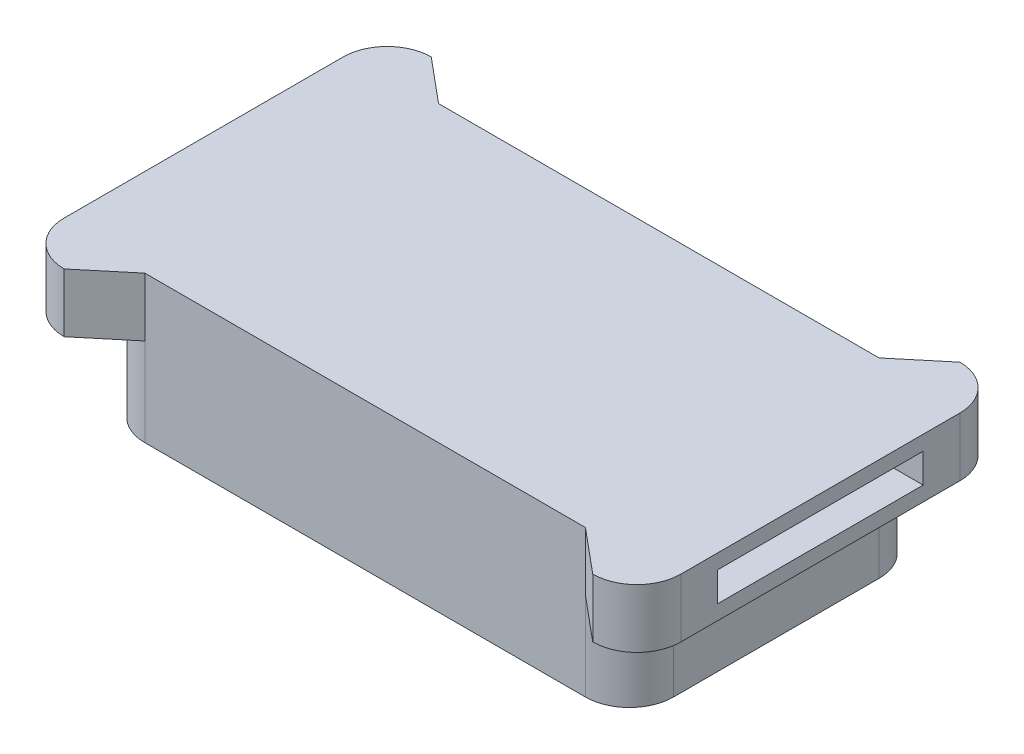
SolidWorks part; units mm, degrees
ref_plane "Front Plane" through (0, 0, 0) normal (0, 0, 1) x (1, 0, 0)
ref_plane "Top Plane" through (0, 0, 0) normal (0, 1, 0) x (1, 0, 0)
ref_plane "Right Plane" through (0, 0, 0) normal (1, 0, 0) x (0, 0, -1)
sketch "Sketch2" plane through (0, 0, 0) normal (0, 1, 0) x (1, 0, 0)
  line L4 (-9, 6.25) -> (-7.5, 5)
  line L5 (-7.5, 5) -> (7.5, 5)
  line L6 (-9, 3.5) -> (-9, -3.5)
  line L11 (-7.5, -5) -> (7.5, -5)
  line L12 (9, 3.5) -> (9, -3.5)
  line L13 (-9, 5) -> (9, -5) construction
  line L14 (-9, -5) -> (9, 5) construction
  line L16 (-10.5, 4.75) -> (-10.5, -4.75)
  line L18 (10.5, 4.75) -> (10.5, -4.75)
  line L19 (-10.5, 6.25) -> (10.5, -6.25) construction
  line L20 (-10.5, -6.25) -> (10.5, 6.25) construction
  line L21 (6.75, 4.25) -> (-6.75, 4.25)
  line L22 (8.25, 2.75) -> (8.25, -2.75)
  line L23 (6.75, -4.25) -> (-6.75, -4.25)
  line L24 (-8.25, 2.75) -> (-8.25, -2.75)
  line L25 (8.25, 4.25) -> (-8.25, -4.25) construction
  line L26 (8.25, -4.25) -> (-8.25, 4.25) construction
  line L27 (7.5, 5) -> (9, 6.25)
  line L28 (-7.5, -5) -> (-9, -6.25)
  line L29 (7.5, -5) -> (9, -6.25)
  arc A8 (-7.5, -5) -> (-9, -3.5) centre (-7.5, -3.5) cw
  arc A9 (7.5, -5) -> (9, -3.5) centre (7.5, -3.5) ccw
  arc A10 (9, 3.5) -> (7.5, 5) centre (7.5, 3.5) ccw
  arc A11 (-7.5, 5) -> (-9, 3.5) centre (-7.5, 3.5) ccw
  arc A12 (9, 6.25) -> (10.5, 4.75) centre (9, 4.75) cw
  arc A13 (9, -6.25) -> (10.5, -4.75) centre (9, -4.75) ccw
  arc A14 (-9, -6.25) -> (-10.5, -4.75) centre (-9, -4.75) cw
  arc A15 (-10.5, 4.75) -> (-9, 6.25) centre (-9, 4.75) cw
  arc A16 (6.75, 4.25) -> (8.25, 2.75) centre (6.75, 2.75) cw
  arc A17 (8.25, -2.75) -> (6.75, -4.25) centre (6.75, -2.75) cw
  arc A18 (-6.75, -4.25) -> (-8.25, -2.75) centre (-6.75, -2.75) cw
  arc A19 (-8.25, 2.75) -> (-6.75, 4.25) centre (-6.75, 2.75) cw
  point P5 (0, 0)
  point P6 (0, 0)
  point P35 (0, 0)
  dimension "D1" = 1.5
  dimension "D6" = 10
  dimension "D9" = 1.5
  dimension "D2" = 21
  dimension "D3" = 0
  dimension "D4" = 0
  dimension "D5" = 18
  dimension "D7" = 8.5
  dimension "D8" = 16.5
extrude "Boss-Extrude1" add sketch "Sketch2" along normal blind 2 and the other way blind 3 contours L5 A11 L6 A8 L11 A9 L12 A10 L24 A19 L21 A16 L22 A17 L23 A18 region at (0, 0, -4.7941)
extrude "Boss-Extrude2" add sketch "Sketch2<3>" along normal blind 2 contours A19 L24 A18 L23 A17 L22 A16 L21 region at (0, 0, 0)
sketch "Sketch2<3>" plane through (0, 0, 0) normal (0, 1, 0) x (1, 0, 0) same geometry as "Sketch2"
extrude "Boss-Extrude3" add sketch "Sketch2<4>" along normal blind 2 contours A15 L16 A14 A13 L18 A12 A11 L5 A10 L12 A9 L11 A8 L6 | L29 A13 L18 A12 L27 A10 L12 A9 region at (-9.5661, 0, 0) region at (9.5661, 0, 0)
sketch "Sketch2<4>" plane through (0, 0, 0) normal (0, 1, 0) x (1, 0, 0) same geometry as "Sketch2"
sketch "Sketch3" plane through (-10.5, 0, 0) normal (-1, 0, 0) x (0, 0, 1)
  line L0 (-4.75, 1) -> (4.75, 1) construction
  line L1 (-4.75, 2) -> (-4.75, 0) construction
  line L2 (4.75, 2) -> (4.75, 0) construction
  line L4 (-3.5, 1.5) -> (3.5, 1.5)
  line L5 (-3.5, 1.5) -> (-3.5, 0.5)
  line L6 (-3.5, 0.5) -> (3.5, 0.5)
  line L7 (3.5, 1.5) -> (3.5, 0.5)
  line L8 (-3.5, 1.5) -> (3.5, 0.5) construction
  line L9 (-3.5, 0.5) -> (3.5, 1.5) construction
  point P6 (0, 1)
  dimension "D1" = 7
  dimension "D2" = 1
extrude "Cut-Extrude2" cut sketch "Sketch3" against normal blind 1.2
sketch "Sketch4" plane through (10.5, 0, 0) normal (1, 0, 0) x (0, 0, -1)
  line L0 (-4.75, 1) -> (4.75, 1) construction
  line L1 (-4.75, 2) -> (-4.75, 0) construction
  line L2 (4.75, 2) -> (4.75, 0) construction
  line L4 (-3.5, 1.5) -> (3.5, 1.5)
  line L5 (-3.5, 1.5) -> (-3.5, 0.5)
  line L6 (-3.5, 0.5) -> (3.5, 0.5)
  line L7 (3.5, 1.5) -> (3.5, 0.5)
  line L8 (-3.5, 1.5) -> (3.5, 0.5) construction
  line L9 (-3.5, 0.5) -> (3.5, 1.5) construction
  point P6 (0, 1)
  dimension "D1" = 1
  dimension "D2" = 7
extrude "Cut-Extrude3" cut sketch "Sketch4" against normal blind 1.2
